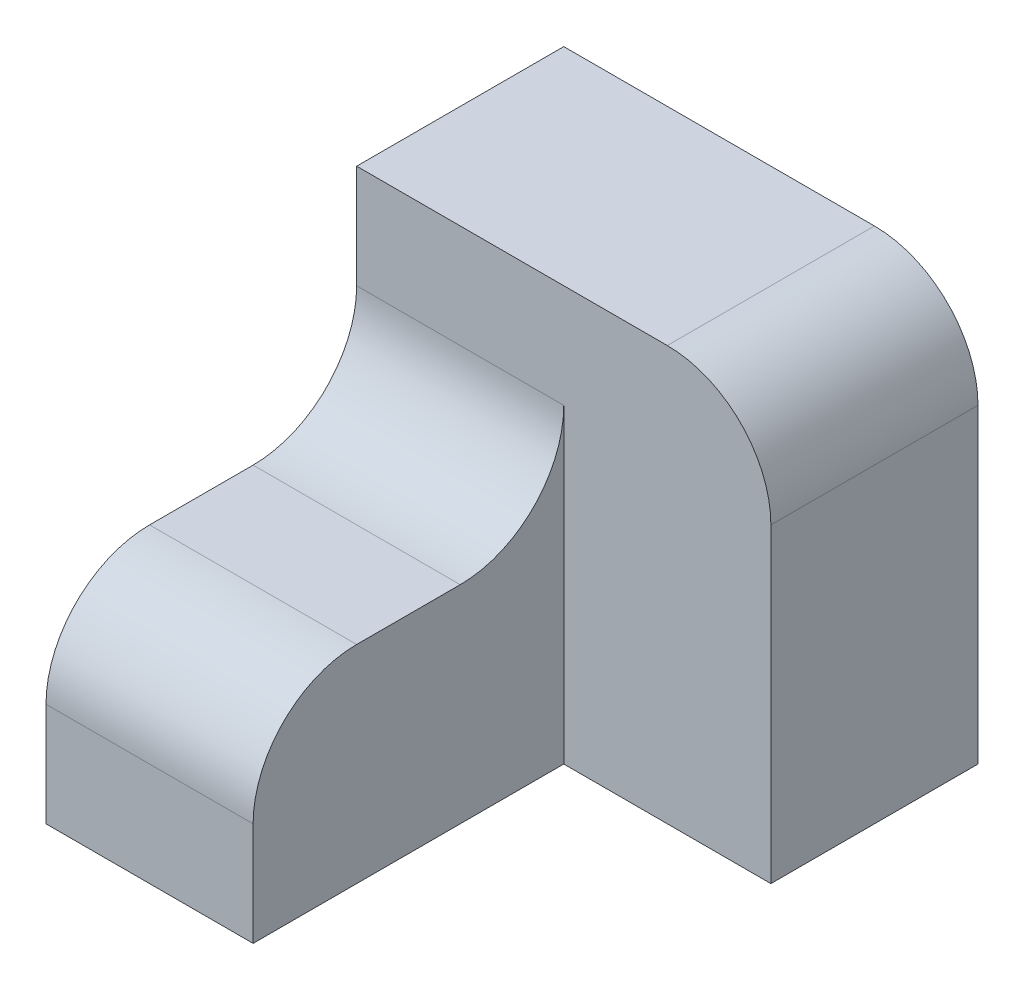
SolidWorks part; units mm, degrees
ref_plane "Front Plane" through (0, 0, 0) normal (0, 0, 1) x (1, 0, 0)
ref_plane "Top Plane" through (0, 0, 0) normal (0, 1, 0) x (1, 0, 0)
ref_plane "Right Plane" through (0, 0, 0) normal (1, 0, 0) x (0, 0, -1)
sketch "Sketch1" plane through (0, 0, 0) normal (1, 0, 0) x (0, 0, -1)
  line L0 (0, 0) -> (50, 0)
  line L1 (50, 0) -> (50, 40)
  line L2 (50, 40) -> (30, 40)
  line L3 (30, 40) -> (30, 20)
  line L4 (30, 20) -> (0, 20)
  line L5 (0, 20) -> (0, 0)
  point P3 (30, 20)
  point P8 (30, 20)
  point P9 (30, 20)
  dimension "D1" = 50
  dimension "D2" = 40
  dimension "D3" = 30
  dimension "D4" = 20
extrude "Boss-Extrude1" add sketch "Sketch1" along normal blind 20
sketch "Sketch2" plane through (20, 0, 0) normal (1, 0, 0) x (0, 0, -1)
  line L0 (30, 40) -> (50, 40)
  line L1 (50, 40) -> (50, 0)
  line L2 (50, 0) -> (50, 40) construction
  line L3 (50, 0) -> (30, 0)
  line L4 (0, 0) -> (50, 0) construction
  line L5 (30, 0) -> (30, 40)
extrude "Boss-Extrude2" add sketch "Sketch2" along normal blind 20
fillet "Fillet1" radius 10 3 edges at (10, 20, -30) (40, 40, -40) (10, 20, 0)
